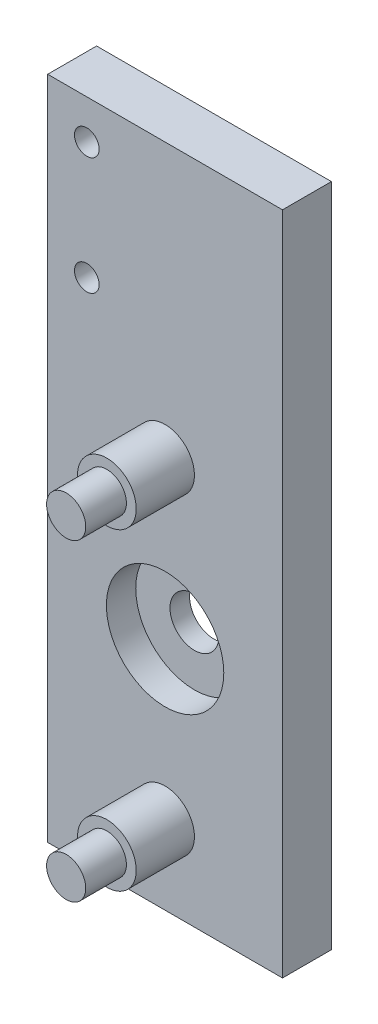
SolidWorks part; units mm, degrees
ref_plane "Front Plane" through (0, 0, 0) normal (0, 0, 1) x (1, 0, 0)
ref_plane "Top Plane" through (0, 0, 0) normal (0, 1, 0) x (1, 0, 0)
ref_plane "Right Plane" through (0, 0, 0) normal (1, 0, 0) x (0, 0, -1)
sketch "Sketch1" plane through (0, 0, 0) normal (0, 0, 1) x (1, 0, 0)
  line L1 (-19.05, -38.1) -> (19.05, -38.1)
  line L2 (-19.05, -38.1) -> (-19.05, 38.1)
  line L3 (-19.05, 38.1) -> (19.05, 38.1)
  line L4 (19.05, -38.1) -> (19.05, 38.1)
  line L5 (-19.05, -38.1) -> (19.05, 38.1) construction
  line L6 (-19.05, 38.1) -> (19.05, -38.1) construction
  point P0 (0, 0)
  dimension "D1" = 38.1
  dimension "D2" = 76.2
extrude "Boss-Extrude1" add sketch "Sketch1" along normal blind 7.9375
sketch "Sketch2" plane through (0, 0, 7.9375) normal (0, 0, 1) x (1, 0, 0)
  circle A0 centre (0, 0) radius 3.9688
  dimension "D1" = 7.9375
extrude "Cut-Extrude1" cut sketch "Sketch2" against normal through all
sketch "Sketch4" plane through (0, 0, 7.9375) normal (0, 0, 1) x (1, 0, 0)
  circle A0 centre (0, 0) radius 9.525
  dimension "D1" = 19.05
extrude "Cut-Extrude2" cut sketch "Sketch4" against normal offset from surface (4.7625 mm away) 3.175 up to face at (3.9688, 0, 0)
sketch "Sketch5" plane through (0, 0, 7.9375) normal (0, 0, 1) x (1, 0, 0)
  line L0 (19.05, 38.1) -> (-19.05, 38.1) construction
  circle A0 centre (0, 25.4) radius 4.7625
  dimension "D1" = 9.525
  dimension "D2" = 12.7
extrude "Boss-Extrude2" add sketch "Sketch5" along normal blind 9.4488
sketch "Sketch6" plane through (0, 0, 17.3863) normal (0, 0, 1) x (1, 0, 0)
  circle A0 centre (0, 25.4) radius 3.175
  dimension "D1" = 6.35
extrude "Boss-Extrude3" add sketch "Sketch6" along normal blind 6.604
mirror "Mirror1" about plane through (0, 0, 0) normal (0, 1, 0) of "Boss-Extrude2", "Boss-Extrude3"
sketch "Sketch7" plane through (0, 0, 7.9375) normal (0, 0, 1) x (1, 0, 0)
  line L1 (-19.05, 38.1) -> (19.05, 38.1)
  line L2 (-19.05, 38.1) -> (-19.05, 69.85)
  line L3 (-19.05, 69.85) -> (19.05, 69.85)
  line L4 (19.05, 38.1) -> (19.05, 69.85)
  line L5 (19.05, -38.1) -> (19.05, 38.1) construction
  line L6 (-19.05, 53.975) -> (19.05, 53.975) construction
  line L7 (-12.7, 69.85) -> (-12.7, 38.1) construction
  circle A0 centre (-12.7, 63.5) radius 2
  circle A1 centre (-12.7, 44.45) radius 2
  dimension "D3" = 4
  dimension "D1" = 31.75
  dimension "D2" = 6.35
  dimension "D4" = 9.525
extrude "Boss-Extrude4" add sketch "Sketch7" against normal up to surface (7.9375 mm away) up to face at (3.9688, 0, 0)
